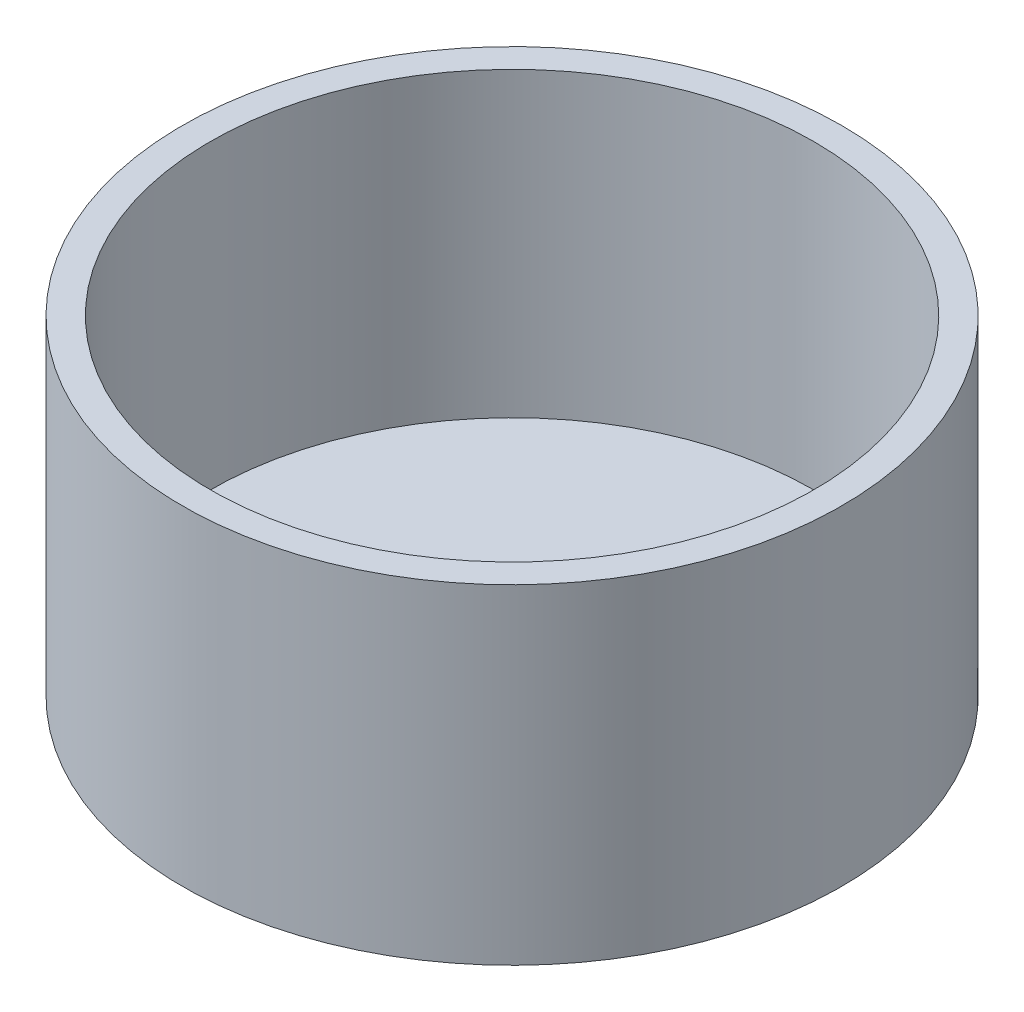
SolidWorks part; units mm, degrees
ref_plane "Front Plane" through (0, 0, 0) normal (0, 0, 1) x (1, 0, 0)
ref_plane "Top Plane" through (0, 0, 0) normal (0, 1, 0) x (1, 0, 0)
ref_plane "Right Plane" through (0, 0, 0) normal (1, 0, 0) x (0, 0, -1)
sketch "Sketch1" plane through (0, 0, 0) normal (0, 1, 0) x (1, 0, 0)
  circle A0 centre (0, 0) radius 54.19
  circle A1 centre (0, 0) radius 59.19
  dimension "D1" = 5
extrude "Boss-Extrude2" add sketch "Sketch1" along normal blind 54.19 contours A0 | A1
extrude "Boss-Extrude3" add sketch "Sketch1<3>" against normal blind 5 contours A0 | A1 A0 region at (0, 0, 0) region at (-57.5159, 0, 0)
sketch "Sketch1<3>" plane through (0, 0, 0) normal (0, 1, 0) x (1, 0, 0) same geometry as "Sketch1"
